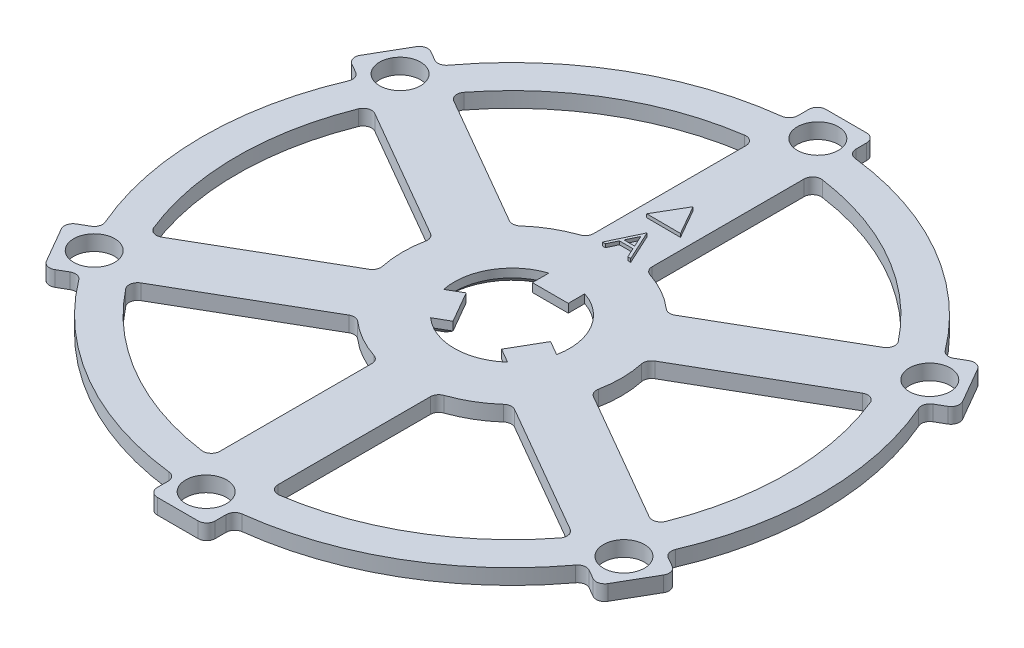
SolidWorks part; units mm, degrees
ref_plane "Front Plane" through (0, 0, 0) normal (0, 0, 1) x (1, 0, 0)
ref_plane "Top Plane" through (0, 0, 0) normal (0, 1, 0) x (1, 0, 0)
ref_plane "Right Plane" through (0, 0, 0) normal (1, 0, 0) x (0, 0, -1)
sketch "Sketch1" plane through (0, 0, 0) normal (0, 1, 0) x (1, 0, 0)
  line L0 (0, 35.3782) -> (0, -23.9127) construction
  line L1 (-12.8, 0) -> (12.8, 0) construction
  line L35 (3.2924, 36.0599) -> (3.2924, 39.2241)
  line L60 (6.6062, -1.3857) -> (4.938, -0.4225)
  line L62 (-2.1031, 6.414) -> (-2.1031, 4.4877)
  line L63 (-2.1031, 4.4877) -> (2.0969, 4.4877)
  line L64 (2.0969, 6.416) -> (2.0969, 4.4877)
  line L68 (4.508, -5.024) -> (2.838, -4.0598)
  line L69 (4.938, -0.4225) -> (2.838, -4.0598)
  line L70 (-4.5031, -5.0283) -> (-2.8349, -4.0652)
  line L72 (-6.6049, -1.3921) -> (-4.9349, -0.4279)
  line L73 (-2.8349, -4.0652) -> (-4.9349, -0.4279)
  line L74 (0, 35.7957) -> (-31, 17.8979) construction
  line L75 (-31, 17.8979) -> (-31, -17.8979) construction
  line L76 (-31, -17.8979) -> (0, -35.7957) construction
  line L77 (0, -35.7957) -> (31, -17.8979) construction
  line L78 (31, -17.8979) -> (31, 17.8979) construction
  line L79 (31, 17.8979) -> (0, 35.7957) construction
  line L81 (3.2924, 12.3693) -> (3.2924, 32.0218)
  line L82 (3.2924, 39.2241) -> (-3.4879, 39.2241)
  line L83 (-3.4879, 12.3156) -> (-3.4879, 32.0011)
  line L84 (0, 22.0676) -> (-3.4879, 39.2241) construction
  line L85 (3.2924, 39.2241) -> (0, 22.0676) construction
  line L86 (-3.4879, 36.0415) -> (-3.4879, 39.2241)
  line L87 (8.9217, 9.1784) -> (25.9698, 19.0211)
  line L88 (12.3584, 3.3333) -> (29.3779, 13.1596)
  line L89 (32.875, 15.1786) -> (35.6152, 16.7607)
  line L90 (29.4689, 21.0413) -> (32.2251, 22.6326)
  line L91 (35.6152, 16.7607) -> (32.2251, 22.6326)
  line L92 (12.4096, -3.1372) -> (29.4577, -12.9799)
  line L93 (9.0659, -9.036) -> (26.0855, -18.8622)
  line L94 (29.5825, -20.8812) -> (32.3228, -22.4634)
  line L95 (32.9568, -15.0001) -> (35.713, -16.5914)
  line L96 (32.3228, -22.4634) -> (35.713, -16.5914)
  line L97 (3.4879, -12.3156) -> (3.4879, -32.0011)
  line L98 (-3.2924, -12.3693) -> (-3.2924, -32.0218)
  line L99 (-3.2924, -36.0599) -> (-3.2924, -39.2241)
  line L100 (3.4879, -36.0415) -> (3.4879, -39.2241)
  line L101 (-3.2924, -39.2241) -> (3.4879, -39.2241)
  line L102 (-8.9217, -9.1784) -> (-25.9698, -19.0211)
  line L103 (-12.3584, -3.3333) -> (-29.3779, -13.1596)
  line L104 (-32.875, -15.1786) -> (-35.6152, -16.7607)
  line L105 (-29.4689, -21.0413) -> (-32.2251, -22.6326)
  line L106 (-35.6152, -16.7607) -> (-32.2251, -22.6326)
  line L107 (-12.4096, 3.1372) -> (-29.4577, 12.9799)
  line L108 (-9.0659, 9.036) -> (-26.0855, 18.8622)
  line L109 (-29.5825, 20.8812) -> (-32.3228, 22.4634)
  line L110 (-32.9568, 15.0001) -> (-35.713, 16.5914)
  line L111 (-32.3228, 22.4634) -> (-35.713, 16.5914)
  arc A0 (-3.4879, 12.3156) -> (-9.0659, 9.036) centre (0, 0) ccw
  arc A5 (-2.1031, 6.414) -> (-6.6049, -1.3921) centre (0, 0) ccw
  arc A6 (-4.5031, -5.0283) -> (4.508, -5.024) centre (0, 0) ccw
  arc A7 (6.6062, -1.3857) -> (2.0969, 6.416) centre (0, 0) ccw
  circle A8 centre (0, 0) radius 31 construction
  circle A9 centre (0, 35.7957) radius 2.4
  arc A10 (-29.4577, 12.9799) -> (-29.3779, -13.1596) centre (0, 0) ccw
  arc A11 (-3.4879, 36.0415) -> (-29.5825, 20.8812) centre (0, 0) ccw
  circle A12 centre (31, 17.8979) radius 2.4
  circle A13 centre (31, -17.8979) radius 2.4
  circle A14 centre (0, -35.7957) radius 2.4
  circle A15 centre (-31, -17.8979) radius 2.4
  circle A16 centre (-31, 17.8979) radius 2.4
  arc A17 (-12.4096, 3.1372) -> (-12.3584, -3.3333) centre (0, 0) ccw
  arc A18 (-8.9217, -9.1784) -> (-3.2924, -12.3693) centre (0, 0) ccw
  arc A19 (3.4879, -12.3156) -> (9.0659, -9.036) centre (0, 0) ccw
  arc A20 (12.4096, -3.1372) -> (12.3584, 3.3333) centre (0, 0) ccw
  arc A21 (8.9217, 9.1784) -> (3.2924, 12.3693) centre (0, 0) ccw
  arc A22 (-25.9698, -19.0211) -> (-3.2924, -32.0218) centre (0, 0) ccw
  arc A23 (3.4879, -32.0011) -> (26.0855, -18.8622) centre (0, 0) ccw
  arc A24 (29.4577, -12.9799) -> (29.3779, 13.1596) centre (0, 0) ccw
  arc A25 (25.9698, 19.0211) -> (3.2924, 32.0218) centre (0, 0) ccw
  arc A26 (-3.4879, 32.0011) -> (-26.0855, 18.8622) centre (0, 0) ccw
  arc A27 (-32.9568, 15.0001) -> (-32.875, -15.1786) centre (0, 0) ccw
  arc A28 (-29.4689, -21.0413) -> (-3.2924, -36.0599) centre (0, 0) ccw
  arc A29 (3.4879, -36.0415) -> (29.5825, -20.8812) centre (0, 0) ccw
  arc A30 (32.9568, -15.0001) -> (32.875, 15.1786) centre (0, 0) ccw
  arc A31 (29.4689, 21.0413) -> (3.2924, 36.0599) centre (0, 0) ccw
  point P3 (0, 9.9)
  point P8 (0, 22.0676)
  point P11 (0, 6.1614)
  point P26 (0, 0)
  point P40 (0, 0)
  point P42 (0, 0)
  point P43 (0, 0)
  point P44 (0, 0)
  point P98 (0, 0)
  dimension "D1" = 62
  dimension "D6" = 3
  dimension "D5" = 4.2
  dimension "D2" = 6
extrude "Boss-Extrude1" add sketch "Sketch1" along normal blind 1.8
ref_plane "Plane1" through (0, 1.2, 0) normal (0, 1, 0) x (1, 0, 0)
sketch "Sketch3" plane through (0, 1.2, 0) normal (0, 1, 0) x (1, 0, 0)
  line L0 (0, 0) -> (0, 34.3448) construction
  line L1 (-3.4879, 14.3853) -> (3.2924, 14.3853) construction
  line L5 (0, 21.2972) -> (-1.4698, 18.7514)
  line L6 (-1.4698, 18.7514) -> (1.4698, 18.7514)
  line L7 (1.4698, 18.7514) -> (0, 21.2972)
  line L8 (-3.4879, 12.3156) -> (-3.4879, 32.0011) construction
  line L9 (3.2924, 32.0218) -> (3.2924, 12.3693) construction
  circle A0 centre (0, 19.6) radius 0.8486 construction
  text T0 "A\r\n"
extrude "Boss-Extrude2" add sketch "Sketch3" along normal blind 0.4
fillet "Fillet1" radius 1 48 edges at (29.4689, 0.9, -21.0413) (3.2924, 0.9, -32.0218) (25.9698, 0.9, -19.0211) (29.3779, 0.9, -13.1596) (29.4577, 0.9, 12.9799) (32.2251, 0.9, -22.6326) (35.6152, 0.9, -16.7607) (32.875, 0.9, -15.1786) (35.713, 0.9, 16.5914) (32.9568, 0.9, 15.0001) (12.3584, 0.9, -3.3333) (12.4096, 0.9, 3.1372) (26.0855, 0.9, 18.8622) (3.4879, 0.9, 32.0011) (32.3228, 0.9, 22.4634) (29.5825, 0.9, 20.8812) (9.0659, 0.9, 9.036) (3.4879, 0.9, 12.3156) (3.4879, 0.9, 36.0415) (3.4879, 0.9, 39.2241) (-3.2924, 0.9, 39.2241) (-3.2924, 0.9, 36.0599) (-3.2924, 0.9, 32.0218) (-8.9217, 0.9, 9.1784) (-3.2924, 0.9, 12.3693) (-25.9698, 0.9, 19.0211) (-29.4689, 0.9, 21.0413) (-32.2251, 0.9, 22.6326) (-35.6152, 0.9, 16.7607) (-32.875, 0.9, 15.1786) (-29.3779, 0.9, 13.1596) (-29.4577, 0.9, -12.9799) (-12.3584, 0.9, 3.3333) (-12.4096, 0.9, -3.1372) (-32.9568, 0.9, -15.0001) (-35.713, 0.9, -16.5914) (8.9217, 0.9, -9.1784) (-32.3228, 0.9, -22.4634) (3.2924, 0.9, -36.0599) (3.2924, 0.9, -39.2241) (3.2924, 0.9, -12.3693) (-26.0855, 0.9, -18.8622) (-3.4879, 0.9, -36.0415) (-29.5825, 0.9, -20.8812) (-3.4879, 0.9, -12.3156) (-9.0659, 0.9, -9.036) (-3.4879, 0.9, -39.2241) (-3.4879, 0.9, -32.0011)
ref_plane "Plane2" through (0, 1.8, 0) normal (0, 1, 0) x (1, 0, 0)
sketch "Sketch4" plane through (0, 1.8, 0) normal (0, 1, 0) x (1, 0, 0)
  line L0 (0, 0) -> (0, 29.1505) construction
  line L1 (-3.0789, 12.2924) -> (2.9677, 12.2924) construction
  line L2 (0.011, 21.1866) -> (-1.9915, 17.7562)
  line L3 (-1.9915, 17.7562) -> (1.9805, 17.7373)
  line L4 (1.9805, 17.7373) -> (0.011, 21.1866)
  circle A0 centre (0, 18.8934) radius 1.1466 construction
  text T0 "A"
extrude "Boss-Extrude3" add sketch "Sketch4" along normal blind 0.4
chamfer "Chamfer1" distance 0.8 angle 45 12 edges at (0.0033, 0, 6.75) (-3.669, 0, 4.5468) (3.673, 0, 4.5419) (3.888, 0, 2.2412) (5.7721, 0, 0.9041) (5.844, 0, -3.3778) (2.0969, 0, -5.4519) (-3.8849, 0, 2.2465) (-5.7699, 0, 0.91) (-5.8473, 0, -3.3722) (-2.1031, 0, -5.4509) (-0.0031, 0, -4.4877)
scale "Scale1" bodies to scale 103 scale about centroid uniform scaling yes scale factor 1.15
